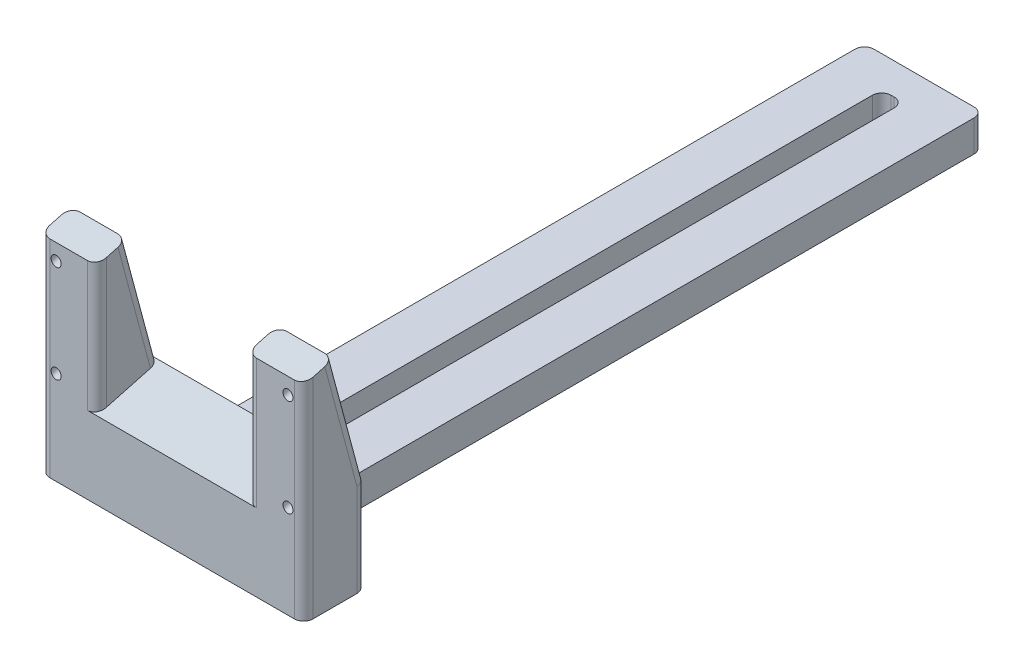
SolidWorks part; units mm, degrees
ref_plane "Front Plane" through (0, 0, 0) normal (0, 0, 1) x (1, 0, 0)
ref_plane "Top Plane" through (0, 0, 0) normal (0, 1, 0) x (1, 0, 0)
ref_plane "Right Plane" through (0, 0, 0) normal (1, 0, 0) x (0, 0, -1)
sketch "Sketch1" plane through (0, 0, 0) normal (0, 1, 0) x (1, 0, 0)
  line L1 (0, 0) -> (-19, 0)
  line L2 (0, 0) -> (0, 120)
  line L3 (0, 120) -> (-19, 120)
  line L4 (-19, 0) -> (-19, 120)
  line L5 (-11.25, 115) -> (-7.75, 115)
  line L6 (-11.25, 115) -> (-11.25, 15)
  line L7 (-11.25, 15) -> (-7.75, 15)
  line L8 (-7.75, 115) -> (-7.75, 15)
  point P9 (-9.5, 115)
  point P10 (-9.5, 120)
  dimension "D1" = 120
  dimension "D2" = 19
  dimension "D3" = 3.5
  dimension "D4" = 5
  dimension "D5" = 100
extrude "Boss-Extrude1" add sketch "Sketch1" along normal blind 5
sketch "Sketch2" plane through (0, 0, 0) normal (1, 0, 0) x (0, 0, -1)
  line L0 (10, 15) -> (4.8236, 34.3185)
  line L2 (0, 5) -> (0, 15)
  line L4 (10, 5) -> (10, 15)
  line L5 (4.8236, 34.3185) -> (0, 33.026)
  line L6 (0, 33.026) -> (0, 15)
  line L8 (0, 0) -> (10, 0)
  line L9 (0, 0) -> (0, 5)
  line L11 (10, 0) -> (10, 5)
  line L13 (0, 5) -> (120, 5) construction
  point P8 (9.8274, 6.8501)
  dimension "D1" = 10
  dimension "D2" = 165
  dimension "D3" = 10
  dimension "D4" = 20
  dimension "D5" = 10
extrude "Boss-Extrude2" add sketch "Sketch2" against normal blind 30.5 and the other way blind 11.5
sketch "Sketch4" plane through (0, 3.5048, -13.0801) normal (0, 0.2588, -0.9659) x (-1, 0, 0)
  line L0 (-11.5, 31.9007) -> (30.5, 31.9007) construction
  line L1 (-2.5, 31.9007) -> (21.5, 31.9007)
  line L2 (-2.5, 31.9007) -> (-2.5, 11.9007)
  line L3 (-2.5, 11.9007) -> (21.5, 11.9007)
  line L4 (21.5, 31.9007) -> (21.5, 11.9007)
  line L5 (-11.5, 11.9007) -> (30.5, 11.9007) construction
  line L6 (-11.5, 11.9007) -> (-11.5, 31.9007) construction
  circle A0 centre (-9, 29.4007) radius 0.8
  circle A1 centre (-9, 14.4007) radius 0.8
  circle A2 centre (28, 14.4007) radius 0.8
  circle A3 centre (28, 29.4007) radius 0.8
  point P16 (9.5, 11.9007)
  point P17 (9.5, 11.9007)
  point P18 (0, 0)
  point P19 (0, 0)
  point P20 (0, 0)
  point P23 (-11.5, 21.9007)
  point P24 (9.5, 31.9007)
  dimension "D6" = 1.6
  dimension "D1" = 24
  dimension "D2" = 37
  dimension "D3" = 15
  dimension "D4" = 7.5
  dimension "D5" = 18.5
extrude "Cut-Extrude2" cut sketch "Sketch4" against normal through all
fillet "Fillet3" radius 1.5 19 edges at (11.5, 7.5, -10) (-21.5, 22.6733, 0) (-30.5, 7.5, -10) (11.5, 24.6593, -7.4118) (-21.5, 24.6593, -7.4118) (-30.5, 24.6593, -7.4118) (11.5, 16.513, 0) (-30.5, 16.513, 0) (2.5, 22.6733, 0) (2.5, 24.6593, -7.4118) (-9.5, 5, -10) (-7.75, 2.5, -15) (-11.25, 2.5, -15) (0, 2.5, -10) (-19, 2.5, -10) (-11.25, 2.5, -115) (-19, 2.5, -120) (-7.75, 2.5, -115) (0, 2.5, -120)
